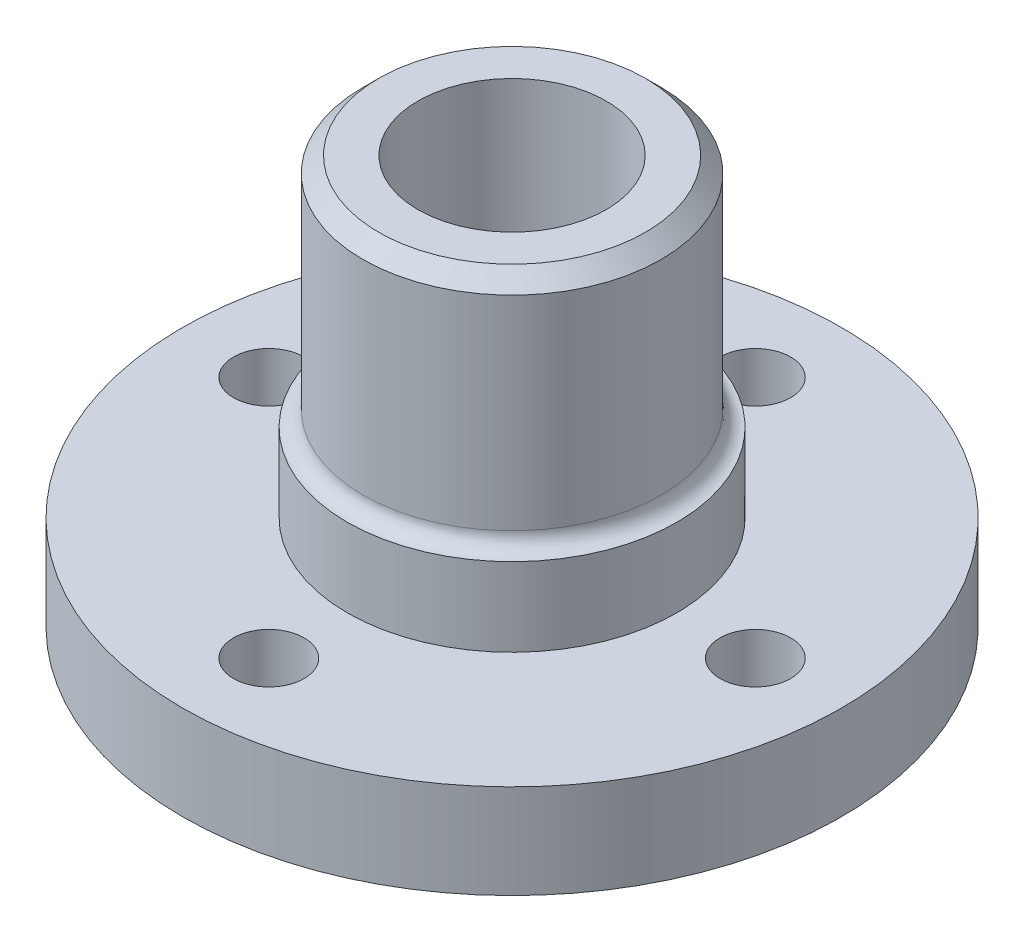
SolidWorks part; units mm, degrees
ref_plane "Piano frontale" through (0, 0, 0) normal (0, 0, 1) x (1, 0, 0)
ref_plane "Piano superiore" through (0, 0, 0) normal (0, 1, 0) x (1, 0, 0)
ref_plane "Piano destro" through (0, 0, 0) normal (1, 0, 0) x (0, 0, -1)
sketch "Schizzo1" plane through (0, 0, 0) normal (0, 0, 1) x (1, 0, 0)
  line L0 (6, 27) -> (6, 0)
  line L1 (6, 0) -> (10, 0)
  line L2 (10, 0) -> (10, 1)
  line L3 (10, 1) -> (21, 1)
  line L4 (21, 1) -> (21, 7)
  line L7 (9.5, 27) -> (6, 27)
  line L8 (9.5, 27) -> (9.5, 12)
  line L9 (9.5, 12) -> (10.5, 12)
  line L11 (10.5, 12) -> (10.5, 7)
  line L12 (10.5, 7) -> (21, 7)
  line L13 (0, 27) -> (0, 0)
  point P7 (9.5, 19.5)
  point P14 (0, 0)
  point P15 (0, 27)
  point P16 (0, 0)
  point P17 (0, 0)
  point P18 (0, 0)
  dimension "D1" = 6
  dimension "D2" = 6
  dimension "D3" = 9.5
  dimension "D4" = 10.5
  dimension "D5" = 10
  dimension "D6" = 11
  dimension "D7" = 1
  dimension "D8" = 27
  dimension "D9" = 21
revolve "Rivoluzione1" add sketch "Schizzo1" angle 360 about L13 region at (7.75, 26.6911, 0)
fillet "Raccordo1" radius 1 1 edges at (0, 12, 9.5)
chamfer "Smusso1" distance 1 angle 45 1 edges at (0, 27, 9.5)
fillet "Raccordo2" radius 1 1 edges at (0, 1, 10)
sketch "Schizzo2" plane through (0, 7, 0) normal (0, 1, 0) x (1, 0, 0)
  line L0 (0, 21) -> (0, -21)
  line L1 (21, 0) -> (-21, 0)
  circle A2 centre (0, 0) radius 21 construction
  circle A3 centre (-15.5, 0) radius 2.25
  circle A4 centre (15.5, 0) radius 2.25
  circle A5 centre (0, 15.5) radius 2.25
  circle A6 centre (0, -15.5) radius 2.25
  dimension "D1" = 4.5
  dimension "D2" = 15.5
  dimension "D3" = 4.5
  dimension "D4" = 15.5
extrude "Taglio-Estrusione1" cut sketch "Schizzo2" against normal through all contours L0 A5 | L0 A5 | A4 L1 | A4 L1 | A6 L0 | A6 L0 | L1 A3 | L1 A3 region at (0.9549, 7, -15.5) region at (15.5, 7, -0.9549) region at (15.5, 7, 0.9549) region at (0.9549, 7, 15.5) region at (-0.9549, 7, 15.5) region at (-15.5, 7, 0.9549) region at (-15.5, 7, -0.9549) region at (-0.9549, 7, -15.5)
